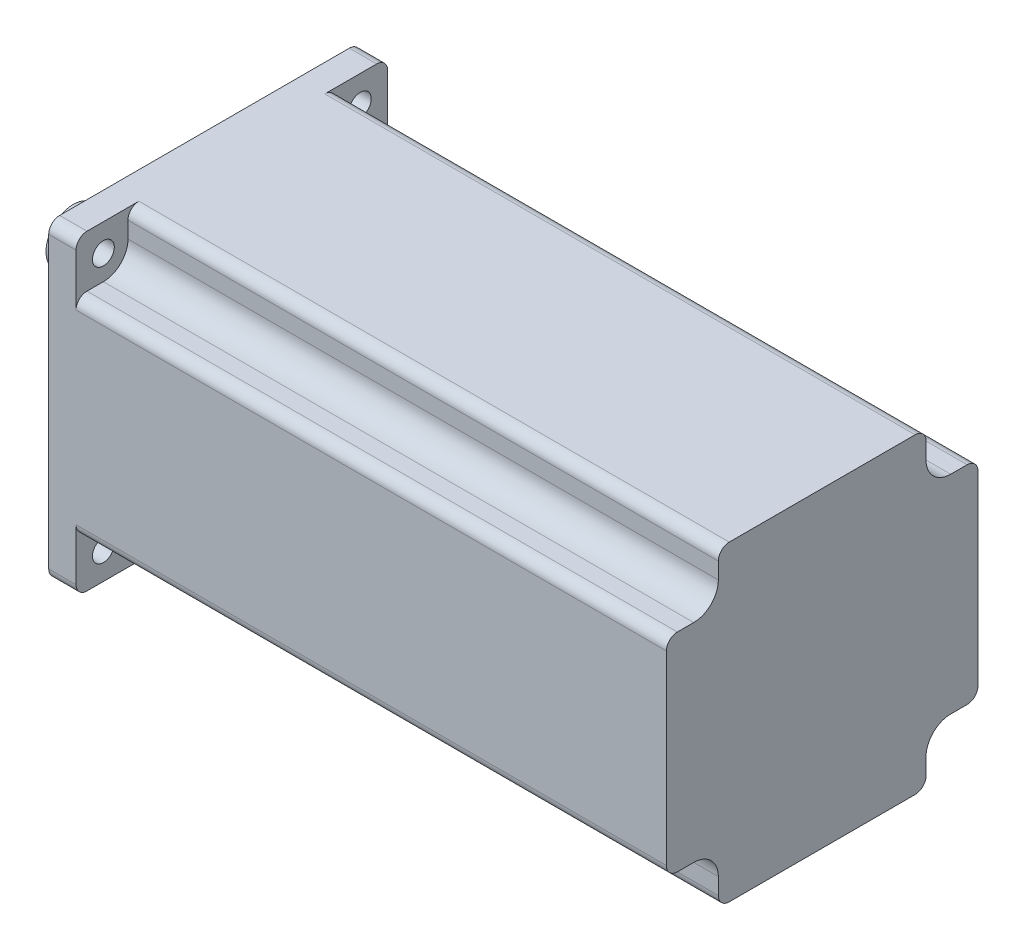
SolidWorks part; units mm, degrees
ref_plane "Front Plane" through (0, 0, 0) normal (0, 0, 1) x (1, 0, 0)
ref_plane "Top Plane" through (0, 0, 0) normal (0, 1, 0) x (1, 0, 0)
ref_plane "Right Plane" through (0, 0, 0) normal (1, 0, 0) x (0, 0, -1)
sketch "Sketch2" plane through (0, 0, 0) normal (0, 1, 0) x (1, 0, 0)
  line L1 (0, 0) -> (113, 0)
  line L2 (0, 0) -> (0, 57)
  line L3 (0, 57) -> (113, 57)
  line L4 (113, 0) -> (113, 57)
extrude "Boss-Extrude1" add sketch "Sketch2" along normal blind 57
sketch "Sketch10" plane through (0, 0, 0) normal (-1, 0, 0) x (0, 0, 1)
  line L1 (-5, 5) -> (-52, 5)
  line L2 (-5, 5) -> (-5, 52)
  line L3 (-5, 52) -> (-52, 52)
  line L4 (-52, 5) -> (-52, 52)
sketch "Sketch11" plane through (0, 0, 0) normal (-1, 0, 0) x (0, 0, 1)
  line L0 (0, 28.5) -> (-57, 28.5) construction
  line L1 (0, 57) -> (0, 0) construction
  line L2 (-57, 57) -> (-57, 0) construction
  line L3 (-28.5, 0) -> (-28.5, 57) construction
  line L4 (-57, 0) -> (0, 0) construction
  line L5 (-57, 57) -> (0, 57) construction
  circle A0 centre (-28.5, 28.5) radius 5
  circle A1 centre (-28.5, 28.5) radius 19
extrude "Boss-Extrude12" add sketch "Sketch11" along normal blind 24 contours A0
extrude "Boss-Extrude13" add sketch "Sketch11<6>" along normal blind 1.6
sketch "Sketch11<6>" plane through (0, 0, 0) normal (-1, 0, 0) x (0, 0, 1) same geometry as "Sketch11"
sketch "Sketch13" plane through (0, 0, 0) normal (-1, 0, 0) x (0, 0, 1)
  circle A0 centre (-5, 5) radius 2
  circle A1 centre (-52, 5) radius 2
  circle A2 centre (-52, 52) radius 2
  circle A3 centre (-5, 52) radius 2
extrude "Cut-Extrude1" cut sketch "Sketch13" against normal blind 113
sketch "Sketch14" plane through (-24, 0, 0) normal (-1, 0, 0) x (0, 0, 1)
  line L0 (-31.3557, 24.3958) -> (-31.2977, 24.356)
  line L1 (-23.5046, 28.2851) -> (-33.4954, 28.2851) construction
  line L2 (-28.5, 23.6076) -> (-28.5, 33.5) construction
  line L3 (-28.5, 24.2078) -> (-28.5, 33.5)
  line L4 (-28.5, 24.2078) -> (-31.0646, 24.2078)
  line L5 (-28.5, 24.2078) -> (-25.9354, 24.2078)
  circle A0 centre (-28.5, 28.5) radius 5 construction
  circle M1 centre (-28.5, 28.5) radius 5
sketch "Sketch16" plane through (0, 57, 0) normal (0, 1, 0) x (1, 0, 0)
  line L1 (5, 5) -> (108, 5)
  line L2 (5, 5) -> (5, 52)
  line L3 (5, 52) -> (108, 52)
  line L4 (108, 5) -> (108, 52)
extrude "Cut-Extrude4" cut sketch "Sketch14" against normal blind 20 contours L5 L4 M1 region at (-24, 23.9229, -28.5)
sketch "Sketch22" plane through (113, 0, 0) normal (1, 0, 0) x (0, 0, -1)
  line L0 (52, 47.5) -> (57, 47.5)
  line L1 (9.5, 47.5) -> (47.5, 47.5)
  line L2 (9.5, 47.5) -> (9.5, 9.5)
  line L3 (9.5, 9.5) -> (47.5, 9.5)
  line L4 (47.5, 47.5) -> (47.5, 9.5)
  line L5 (57, 57) -> (57, 0) construction
  line L6 (52, 9.5) -> (57, 9.5)
  line L7 (47.5, 5) -> (47.5, 0)
  line L8 (0, 0) -> (57, 0) construction
  line L9 (9.5, 5) -> (9.5, 0)
  line L10 (5, 9.5) -> (0, 9.5)
  line L11 (0, 57) -> (0, 0) construction
  line L12 (5, 47.5) -> (0, 47.5) construction
  line L13 (9.5, 52) -> (9.5, 57)
  line L14 (47.5, 52) -> (47.5, 57)
  arc A0 (5, 47.5) -> (9.5, 52) centre (5, 52) ccw
  arc A1 (47.5, 52) -> (52, 47.5) centre (52, 52) ccw
  arc A2 (52, 9.5) -> (47.5, 5) centre (52, 5) ccw
  arc A3 (9.5, 5) -> (5, 9.5) centre (5, 5) ccw
  circle M1 centre (5, 52) radius 2
  circle M2 centre (52, 52) radius 2
  circle M3 centre (52, 5) radius 2
  circle M4 centre (5, 5) radius 2
  line M5 (0, 0) -> (57, 0)
  line M6 (57, 0) -> (57, 57)
  line M7 (57, 57) -> (0, 57)
  line M8 (0, 57) -> (0, 0)
extrude "Cut-Extrude5" cut sketch "Sketch22" against normal blind 108 contours L14 A1 L0 M6 M7 M2 | L12 A0 L13 M7 M8 M1 | L6 A2 L7 M5 M6 M3 | L9 A3 L10 M8 M5 M4 region at (113, 48.913, -48.913) region at (113, 4.75, -56.8656) region at (113, 54.5, -9.3656) region at (113, 0.1344, -4.75)
fillet "Fillet1" radius 2 8 edges at (59, 57, -9.5) (59, 57, -47.5) (59, 47.5, -57) (59, 9.5, -57) (59, 0, -47.5) (59, 0, -9.5) (59, 9.5, 0) (59, 47.5, 0)
fillet "Fillet2" radius 2 4 edges at (2.5, 0, 0) (2.5, 0, -57) (2.5, 57, -57) (2.5, 57, 0)
